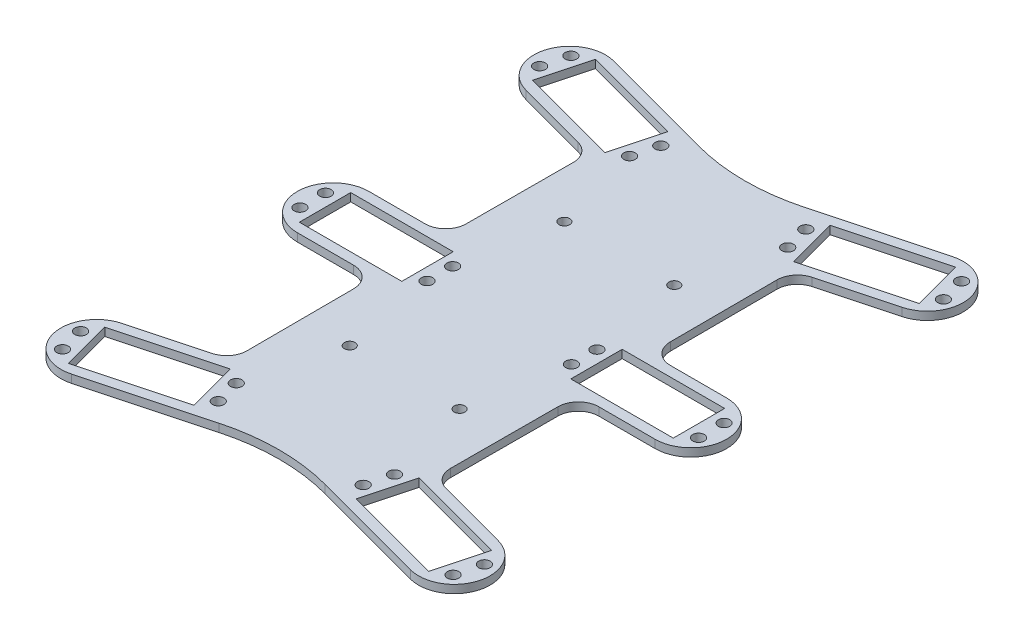
SolidWorks part; units mm, degrees
ref_plane "Front Plane" through (0, 0, 0) normal (0, 0, 1) x (1, 0, 0)
ref_plane "Top Plane" through (0, 0, 0) normal (0, 1, 0) x (1, 0, 0)
ref_plane "Right Plane" through (0, 0, 0) normal (1, 0, 0) x (0, 0, -1)
sketch "Sketch1" plane through (0, 0, 0) normal (0, 1, 0) x (1, 0, 0)
  line L0 (0, 32.1883) -> (0, -21.4181) construction
  line L1 (0, 0) -> (27.1703, 0) construction
  line L2 (-70, 14) -> (-40, 14)
  line L3 (-40, 14) -> (-39.8161, 70)
  line L4 (-39.8161, 70) -> (-73.6235, 79.0587)
  line L5 (-66.3765, 106.1046) -> (0, 88.3191)
  line L10 (-66.3765, 106.1046) -> (-73.6235, 79.0587) construction
  line L12 (-70, 14) -> (-70, -14) construction
  line L14 (-66.3765, -106.1046) -> (0, -88.3191)
  line L15 (-39.8161, -70) -> (-73.6235, -79.0587)
  line L16 (-40, -14) -> (-39.8161, -70)
  line L17 (-70, -14) -> (-40, -14)
  line L18 (66.3765, -106.1046) -> (0, -88.3191)
  line L19 (66.3765, 106.1046) -> (0, 88.3191)
  line L20 (70, 14) -> (70, -14) construction
  line L21 (66.3765, 106.1046) -> (73.6235, 79.0587) construction
  line L22 (70, -14) -> (40, -14)
  line L23 (40, -14) -> (39.8161, -70)
  line L24 (39.8161, -70) -> (73.6235, -79.0587)
  line L25 (39.8161, 70) -> (73.6235, 79.0587)
  line L26 (40, 14) -> (39.8161, 70)
  line L27 (70, 14) -> (40, 14)
  line L28 (-70.4609, 103.1096) -> (-75.6631, 83.6945)
  line L29 (-75.6631, 83.6945) -> (-36.9295, 73.3159)
  line L30 (-36.9295, 73.3159) -> (-31.7272, 92.731)
  line L31 (-31.7272, 92.731) -> (-70.4609, 103.1096)
  line L32 (-51.094, 97.9203) -> (-56.2963, 78.5052) construction
  line L33 (-70, 92.5816) -> (-73.062, 93.4021) construction
  line L34 (-53.12, 10.05) -> (-53.12, -10.05) construction
  line L35 (-73.17, 10.05) -> (-33.07, 10.05)
  line L36 (-73.17, 10.05) -> (-73.17, -10.05)
  line L37 (-73.17, -10.05) -> (-33.07, -10.05)
  line L38 (-33.07, 10.05) -> (-33.07, -10.05)
  line L39 (-73.17, 10.05) -> (-33.07, -10.05) construction
  line L40 (-73.17, -10.05) -> (-33.07, 10.05) construction
  line L41 (-36.9295, -73.3159) -> (-31.7272, -92.731)
  line L42 (-31.7272, -92.731) -> (-70.4609, -103.1096)
  line L43 (-70.4609, -103.1096) -> (-75.6631, -83.6945)
  line L44 (-75.6631, -83.6945) -> (-36.9295, -73.3159)
  line L45 (36.9295, 73.3159) -> (31.7272, 92.731)
  line L46 (75.6631, 83.6945) -> (36.9295, 73.3159)
  line L47 (70.4609, 103.1096) -> (75.6631, 83.6945)
  line L48 (31.7272, 92.731) -> (70.4609, 103.1096)
  line L49 (73.17, -10.05) -> (33.07, 10.05) construction
  line L50 (73.17, 10.05) -> (33.07, -10.05) construction
  line L51 (53.12, 10.05) -> (53.12, -10.05) construction
  line L52 (33.07, 10.05) -> (33.07, -10.05)
  line L53 (73.17, -10.05) -> (33.07, -10.05)
  line L54 (73.17, 10.05) -> (73.17, -10.05)
  line L55 (73.17, 10.05) -> (33.07, 10.05)
  line L56 (36.9295, -73.3159) -> (31.7272, -92.731)
  line L57 (75.6631, -83.6945) -> (36.9295, -73.3159)
  line L58 (31.7272, -92.731) -> (70.4609, -103.1096)
  line L59 (70.4609, -103.1096) -> (75.6631, -83.6945)
  line L60 (-76.4333, 99.4818) -> (-79.0215, 89.8226) construction
  line L61 (-77.7274, 94.6522) -> (-70, 92.5816) construction
  line L62 (-78, 5) -> (-78, -5) construction
  arc A0 (-70, 14) -> (-70, -14) centre (-70, 0) ccw
  arc A1 (-66.3765, 106.1046) -> (-73.6235, 79.0587) centre (-70, 92.5816) ccw
  circle A8 centre (-76.4333, 99.4818) radius 2.25
  circle A9 centre (-79.0215, 89.8226) radius 2.25
  circle A10 centre (-78, 5) radius 2.25
  arc A11 (-66.3765, -106.1046) -> (-73.6235, -79.0587) centre (-70, -92.5816) cw
  circle A12 centre (-79.0215, -89.8226) radius 2.25
  circle A13 centre (-76.4333, -99.4818) radius 2.25
  circle A14 centre (-78, -5) radius 2.25
  circle A15 centre (78, -5) radius 2.25
  circle A16 centre (76.4333, -99.4818) radius 2.25
  circle A17 centre (79.0215, -89.8226) radius 2.25
  arc A18 (66.3765, -106.1046) -> (73.6235, -79.0587) centre (70, -92.5816) ccw
  circle A19 centre (78, 5) radius 2.25
  circle A20 centre (79.0215, 89.8226) radius 2.25
  circle A21 centre (76.4333, 99.4818) radius 2.25
  arc A22 (66.3765, 106.1046) -> (73.6235, 79.0587) centre (70, 92.5816) cw
  arc A23 (70, 14) -> (70, -14) centre (70, 0) cw
  circle A24 centre (-30.957, 76.9437) radius 2.25
  circle A25 centre (-28.3688, 86.603) radius 2.25
  circle A26 centre (-28.24, -5) radius 2.25
  circle A27 centre (-28.24, 5) radius 2.25
  circle A28 centre (-28.3688, -86.603) radius 2.25
  circle A29 centre (-30.957, -76.9437) radius 2.25
  circle A30 centre (28.3688, 86.603) radius 2.25
  circle A31 centre (30.957, 76.9437) radius 2.25
  circle A32 centre (28.24, 5) radius 2.25
  circle A33 centre (28.24, -5) radius 2.25
  circle A34 centre (30.957, -76.9437) radius 2.25
  circle A35 centre (28.3688, -86.603) radius 2.25
  point P60 (-51.094, 97.9203)
  point P62 (-56.2963, 78.5052)
  point P65 (-73.062, 93.4021)
  point P71 (-53.12, 0)
  point P108 (53.12, 0)
  point P118 (-83.523, 96.2051)
  dimension "D2" = 14
  dimension "D3" = 10
  dimension "D8" = 4.5
  dimension "D1" = 75
  dimension "D4" = 70
  dimension "D5" = 30
  dimension "D6" = 35
  dimension "D7" = 56
  dimension "D9" = 8
  dimension "D10" = 5
  dimension "D11" = 10
  dimension "D12" = 40.1
  dimension "D13" = 20.1
  dimension "D14" = 4.83
  dimension "D15" = 40.1
  dimension "D16" = 20.1
  dimension "D17" = 4.83
  dimension "D18" = 8
extrude "Boss-Extrude1" add sketch "Sketch1" along normal blind 3.175
fillet "Fillet1" radius 80 2 edges at (0, 1.5875, -88.3191) (0, 1.5875, 88.3191)
fillet "Fillet2" radius 8 8 edges at (39.8161, 1.5875, 70) (40, 1.5875, 14) (40, 1.5875, -14) (39.8161, 1.5875, -70) (-39.8161, 1.5875, -70) (-40, 1.5875, -14) (-40, 1.5875, 14) (-39.8161, 1.5875, 70)
sketch "Sketch4" plane through (0, 3.175, 0) normal (0, 1, 0) x (1, 0, 0)
  circle A0 centre (-21.5, 42) radius 2.1 construction
  circle A1 centre (-21.5, 42) radius 2.1
  circle A2 centre (21.5, 42) radius 2.1 construction
  circle A3 centre (21.5, -42) radius 2.1 construction
  circle A4 centre (-21.5, -42) radius 2.1 construction
  circle A5 centre (21.5, 42) radius 2.1
  circle A6 centre (21.5, -42) radius 2.1
  circle A7 centre (-21.5, -42) radius 2.1
extrude "Cut-Extrude1" cut sketch "Sketch4" against normal through all
